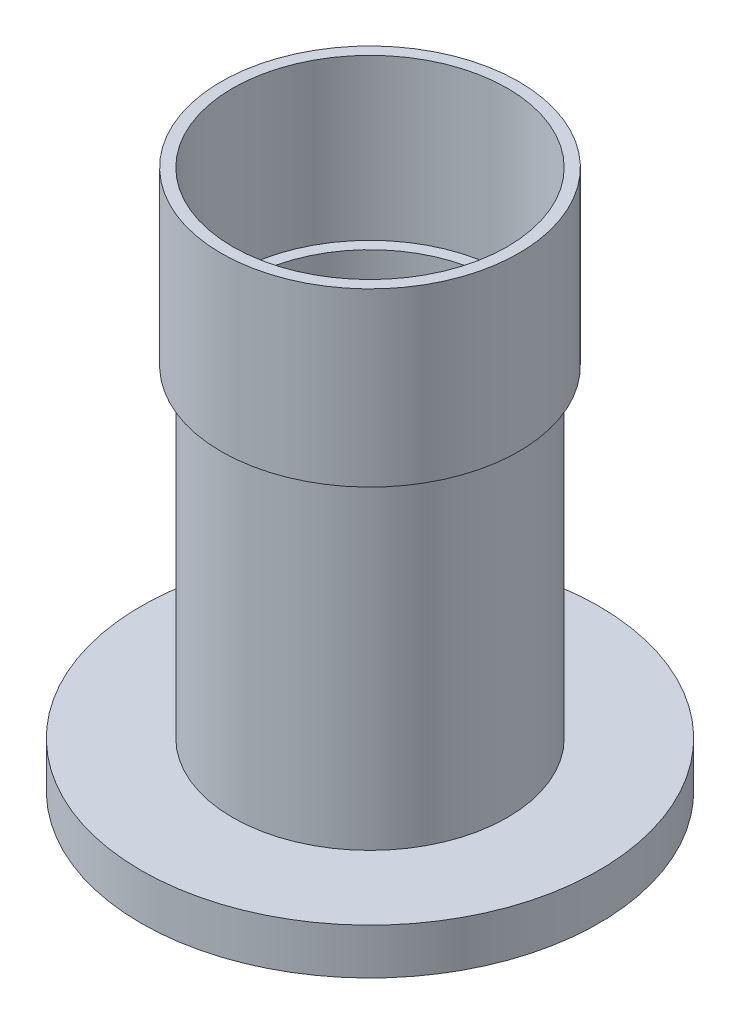
SolidWorks part; units mm, degrees
ref_plane "Front Plane" through (0, 0, 0) normal (0, 0, 1) x (1, 0, 0)
ref_plane "Top Plane" through (0, 0, 0) normal (0, 1, 0) x (1, 0, 0)
ref_plane "Right Plane" through (0, 0, 0) normal (1, 0, 0) x (0, 0, -1)
sketch "Sketch1" plane through (0, 0, 0) normal (0, 1, 0) x (1, 0, 0)
  circle A0 centre (0, 0) radius 31.75
  dimension "D1" = 63.5
extrude "Boss-Extrude1" add sketch "Sketch1" along normal blind 6.35
sketch "Sketch2" plane through (0, 0, 0) normal (0, 0, 1) x (1, 0, 0)
  line L0 (0, -26.0675) -> (0, 48.7435) construction
  line L2 (31.75, 6.35) -> (-31.75, 6.35) construction
  line L3 (19.05, 6.35) -> (19.05, 51.1175)
  line L4 (19.05, 51.1175) -> (20.6375, 51.1175)
  line L5 (20.6375, 51.1175) -> (20.6375, 74.93)
  line L6 (20.6375, 74.93) -> (19.05, 74.93)
  line L7 (19.05, 74.93) -> (19.05, 52.705)
  line L8 (19.05, 52.705) -> (17.4625, 52.705)
  line L9 (17.4625, 52.705) -> (17.4625, 6.35)
  line L10 (17.4625, 6.35) -> (19.05, 6.35)
  dimension "D1" = 34.925
  dimension "D2" = 38.1
  dimension "D3" = 38.1
  dimension "D4" = 41.275
  dimension "D5" = 1.5875
  dimension "D6" = 46.355
  dimension "D7" = 22.225
revolve "Revolve1" add sketch "Sketch2" angle 360 about L0
